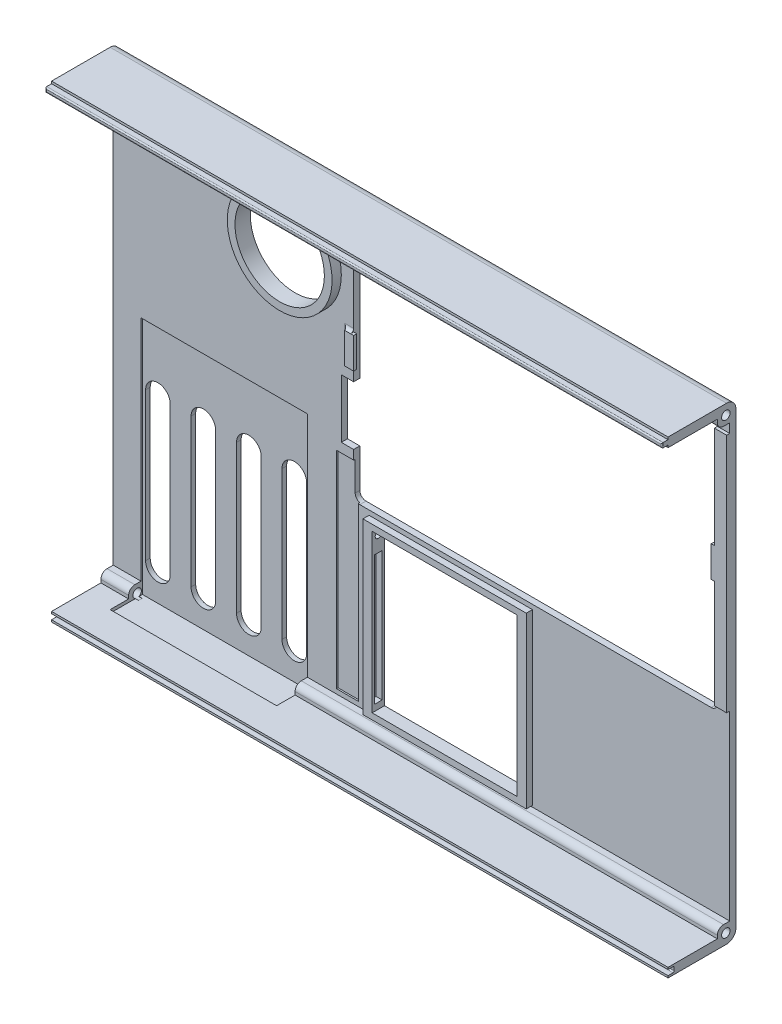
SolidWorks part; units mm, degrees
ref_plane "Front Plane" through (0, 0, 0) normal (0, 0, 1) x (1, 0, 0)
ref_plane "Top Plane" through (0, 0, 0) normal (0, 1, 0) x (1, 0, 0)
ref_plane "Right Plane" through (0, 0, 0) normal (1, 0, 0) x (0, 0, -1)
sketch "Sketch1" plane through (0, 0, 0) normal (0, 0, 1) x (1, 0, 0)
  line L1 (105, -90.3987) -> (-95, -90.3987)
  line L2 (105, -90.3987) -> (105, 61.6013)
  line L3 (105, 61.6013) -> (-95, 61.6013)
  line L4 (-95, -90.3987) -> (-95, 61.6013)
  line L5 (105, -90.3987) -> (-95, 61.6013) construction
  line L6 (105, 61.6013) -> (-95, -90.3987) construction
  point P0 (5, -14.3987)
  dimension "D1" = 200
  dimension "D2" = 152
extrude "body" add sketch "Sketch1" along normal blind 2
sketch "Sketch3" plane through (0, 0, 0) normal (0, 0, -1) x (-1, 0, 0)
  line L0 (95, -54.3987) -> (-105, -54.3987) construction
  line L1 (95, 61.6013) -> (95, -90.3987) construction
  line L2 (-105, -90.3987) -> (-105, 61.6013) construction
  line L3 (66.25, -78.3987) -> (66.25, -30.3987) construction
  line L4 (62.25, -78.3987) -> (62.25, -30.3987)
  line L5 (70.25, -78.3987) -> (70.25, -30.3987)
  line L6 (95, -30.3987) -> (-105, -30.3987) construction
  line L7 (81, -78.3987) -> (81, -30.3987) construction
  line L8 (95, -78.3987) -> (-105, -78.3987) construction
  line L9 (77, -78.3987) -> (77, -30.3987)
  line L10 (85, -78.3987) -> (85, -30.3987)
  line L11 (51.5, -78.3987) -> (51.5, -30.3987) construction
  line L12 (47.5, -78.3987) -> (47.5, -30.3987)
  line L13 (55.5, -78.3987) -> (55.5, -30.3987)
  line L14 (36.75, -78.3987) -> (36.75, -30.3987) construction
  line L15 (32.75, -78.3987) -> (32.75, -30.3987)
  line L16 (40.75, -78.3987) -> (40.75, -30.3987)
  line L17 (95, -90.3987) -> (95, 61.6013) construction
  line L18 (-105, 61.6013) -> (95, 61.6013) construction
  line L19 (95, -90.3987) -> (-105, -90.3987) construction
  line L20 (-105, -90.3987) -> (-105, 61.6013) construction
  circle A0 centre (38, 34.1013) radius 14.5
  arc A1 (62.25, -78.3987) -> (70.25, -78.3987) centre (66.25, -78.3987) ccw
  arc A2 (70.25, -30.3987) -> (62.25, -30.3987) centre (66.25, -30.3987) ccw
  arc A3 (77, -78.3987) -> (85, -78.3987) centre (81, -78.3987) ccw
  arc A4 (85, -30.3987) -> (77, -30.3987) centre (81, -30.3987) ccw
  arc A5 (47.5, -78.3987) -> (55.5, -78.3987) centre (51.5, -78.3987) ccw
  arc A6 (55.5, -30.3987) -> (47.5, -30.3987) centre (51.5, -30.3987) ccw
  arc A7 (32.75, -78.3987) -> (40.75, -78.3987) centre (36.75, -78.3987) ccw
  arc A8 (40.75, -30.3987) -> (32.75, -30.3987) centre (36.75, -30.3987) ccw
  point P10 (66.25, -54.3987)
  point P21 (81, -54.3987)
  point P27 (51.5, -54.3987)
  point P34 (36.75, -54.3987)
  dimension "D1" = 29
  dimension "D2" = 27.5
  dimension "D3" = 57
  dimension "D4" = 10
  dimension "D5" = 12
  dimension "D6" = 24
  dimension "D7" = 6.75
  dimension "D8" = 8
  dimension "D9" = 8
  dimension "D10" = 8
  dimension "D11" = 8
  dimension "D12" = 6.75
  dimension "D13" = 52.25
  dimension "D14" = 6.75
extrude "fan_exhaust_grill" cut sketch "Sketch3" against normal through all
sketch "Sketch12" plane through (0, 0, 2) normal (0, 0, 1) x (1, 0, 0)
  line L0 (-95, -90.3987) -> (-95, 61.6013) construction
  line L1 (105, -90.3987) -> (-95, -90.3987)
  line L2 (105, -90.3987) -> (105, -84.3987)
  line L3 (105, -84.3987) -> (-95, -84.3987)
  line L4 (-95, -90.3987) -> (-95, -84.3987)
  line L6 (105, 61.6013) -> (-95, 61.6013)
  line L7 (105, 61.6013) -> (105, 55.6013)
  line L8 (105, 55.6013) -> (-95, 55.6013)
  line L9 (-95, 61.6013) -> (-95, 55.6013)
  dimension "D1" = 6
  dimension "D2" = 6
extrude "side_walls" add sketch "Sketch12" along normal blind 20
sketch "Sketch14" plane through (105, 0, 0) normal (1, 0, 0) x (0, 0, -1)
  line L0 (-22, -90.3987) -> (0, -90.3987) construction
  line L1 (0, -90.3987) -> (0, 61.6013) construction
  line L2 (-22, 61.6013) -> (0, 61.6013) construction
  circle A0 centre (-3.25, -87.1487) radius 1.375
  circle A1 centre (-3.25, 58.3513) radius 1.375
  dimension "D1" = 2.75
  dimension "D2" = 2.75
  dimension "D3" = 3.25
  dimension "D4" = 3.25
  dimension "D5" = 3.25
  dimension "D6" = 3.25
  dimension "D7" = 145.5
extrude "mount_holes_l" cut sketch "Sketch14" against normal blind 10 and the other way through all
sketch "Sketch16" plane through (-95, 0, 0) normal (-1, 0, 0) x (0, 0, 1)
  line L0 (0, -90.3987) -> (0, 61.6013) construction
  line L2 (22, 61.6013) -> (0, 61.6013) construction
  line L3 (22, -90.3987) -> (0, -90.3987) construction
  circle A0 centre (3.25, -87.1487) radius 1.375
  circle A1 centre (3.25, 58.3513) radius 1.375
  dimension "D1" = 2.75
  dimension "D4" = 2.75
  dimension "D2" = 3.25
  dimension "D3" = 3.25
  dimension "D5" = 3.25
  dimension "D6" = 3.25
extrude "mount_holes_r" cut sketch "Sketch16" against normal blind 10
sketch "Sketch18" plane through (105, 0, 0) normal (1, 0, 0) x (0, 0, -1)
  line L1 (-22, -84.3987) -> (-6, -84.3987)
  line L2 (-22, -84.3987) -> (-22, -87.3987)
  line L3 (-22, -87.3987) -> (-6, -87.3987)
  line L4 (-6, -84.3987) -> (-6, -87.3987)
  line L5 (-22, 55.6013) -> (-6, 55.6013)
  line L6 (-22, 55.6013) -> (-22, 58.6013)
  line L7 (-22, 58.6013) -> (-6, 58.6013)
  line L8 (-6, 55.6013) -> (-6, 58.6013)
  dimension "D1" = 3
  dimension "D2" = 16
  dimension "D3" = 3
  dimension "D4" = 16
extrude "wall_reduce" cut sketch "Sketch18" against normal through all
sketch "Sketch19" plane through (0, 0, 22) normal (0, 0, 1) x (1, 0, 0)
  line L0 (-95, -90.3987) -> (-95, 61.6013) construction
  line L1 (-95, -89.7487) -> (105, -89.7487)
  line L2 (-95, -89.7487) -> (-95, -88.0487)
  line L3 (-95, -88.0487) -> (105, -88.0487)
  line L4 (105, -89.7487) -> (105, -88.0487)
  line L5 (105, -90.3987) -> (105, 61.6013) construction
  line L6 (-95, -90.3987) -> (105, -90.3987) construction
  line L7 (-95, -87.3987) -> (105, -87.3987) construction
  dimension "D1" = 0.65
  dimension "D2" = 1.7
  dimension "D3" = 0.65
extrude "groove" cut sketch "Sketch19" against normal blind 2
sketch "Sketch20" plane through (0, 0, 22) normal (0, 0, 1) x (1, 0, 0)
  line L0 (-95, -90.3987) -> (-95, 61.6013) construction
  line L1 (-95, 59.3513) -> (105, 59.3513)
  line L2 (-95, 59.3513) -> (-95, 60.8513)
  line L3 (-95, 60.8513) -> (105, 60.8513)
  line L4 (105, 59.3513) -> (105, 60.8513)
  line L5 (105, -90.3987) -> (105, 61.6013) construction
  line L6 (105, 61.6013) -> (-95, 61.6013) construction
  dimension "D1" = 0.75
  dimension "D2" = 1.5
extrude "notch" add sketch "Sketch20" along normal blind 2
sketch "Sketch21" plane through (0, 0, 2) normal (0, 0, 1) x (1, 0, 0)
  line L0 (105, -90.3987) -> (105, 61.6013) construction
  line L1 (101, -27.3987) -> (-17, -27.3987)
  line L2 (101, -27.3987) -> (101, 55.1013)
  line L3 (101, 55.1013) -> (-17, 55.1013)
  line L4 (-17, -27.3987) -> (-17, 55.1013)
  line L5 (105, 61.6013) -> (-95, 61.6013) construction
  dimension "D1" = 118
  dimension "D2" = 82.5
  dimension "D3" = 4
  dimension "D4" = 6.5
extrude "batt_cut" cut sketch "Sketch21" against normal through all
fillet "Fillet1" radius 3 2 edges at (5, -90.3987, 0) (5, 61.6013, 0)
fillet "Fillet2" radius 2 2 edges at (5, -84.3987, 6) (5, 55.6013, 6)
fillet "Fillet3" radius 0.4 6 edges at (5, 60.8513, 24) (105, 60.1013, 24) (5, 59.3513, 24) (-95, 60.1013, 24) (5, -89.7487, 20) (5, -88.0487, 20)
fillet "Fillet4" radius 2 4 edges at (-17, -27.3987, 1) (101, -27.3987, 1) (101, 55.1013, 1) (-17, 55.1013, 1)
sketch "Sketch22" plane through (0, 0, 2) normal (0, 0, 1) x (1, 0, 0)
  circle A0 centre (-38, 34.1013) radius 14.5
  circle A1 centre (-38, 34.1013) radius 17
  dimension "D1" = 29
  dimension "D2" = 34
extrude "fan_hole_supp" add sketch "Sketch22" along normal blind 3
sketch "Sketch23" plane through (0, 0, 2) normal (0, 0, 1) x (1, 0, 0)
  line L0 (105, -90.3987) -> (105, 61.6013) construction
  line L1 (105, 52.6013) -> (101, 52.6013)
  line L2 (105, 52.6013) -> (105, -25.3987)
  line L3 (105, -25.3987) -> (101, -25.3987)
  line L4 (101, 52.6013) -> (101, -25.3987)
  arc A0 (99, -27.3987) -> (101, -25.3987) centre (99, -25.3987) ccw construction
  dimension "D1" = 78
  dimension "D2" = 4
extrude "batt_cut_supp" add sketch "Sketch23" along normal blind 1
sketch "Sketch24" plane through (0, 0, 2) normal (0, 0, 1) x (1, 0, 0)
  line L0 (-95, -90.3987) -> (-95, 61.6013) construction
  line L1 (-86, -10.3987) -> (-32, -10.3987)
  line L2 (-86, -10.3987) -> (-86, -88.3987)
  line L3 (-86, -88.3987) -> (-32, -88.3987)
  line L4 (-32, -10.3987) -> (-32, -88.3987)
  line L5 (-95, -90.3987) -> (105, -90.3987) construction
  line L7 (-22.5, -15.8987) -> (-15.5, -15.8987)
  line L8 (-22.5, -15.8987) -> (-22.5, -82.8987)
  line L9 (-22.5, -82.8987) -> (-15.5, -82.8987)
  line L10 (-15.5, -15.8987) -> (-15.5, -82.8987)
  dimension "D1" = 9
  dimension "D2" = 2
  dimension "D3" = 54
  dimension "D4" = 78
  dimension "D5" = 9.5
  dimension "D6" = 7
  dimension "D7" = 67
  dimension "D8" = 5.5
  dimension "D9" = 5.5
extrude "Cut-Extrude1" cut sketch "Sketch24" against normal blind 10.5 from offset 10
sketch "Sketch25" plane through (0, 0, 2) normal (0, 0, 1) x (1, 0, 0)
  line L7 (-17, 53.1013) -> (-17, -15.8987) construction
  line L8 (-17, 6.1013) -> (-21, 6.1013)
  line L9 (-17, 6.1013) -> (-17, -12.8987)
  line L10 (-17, -12.8987) -> (-21, -12.8987)
  line L11 (-21, 6.1013) -> (-21, -12.8987)
  line L12 (-15, -27.3987) -> (99, -27.3987) construction
  dimension "D1" = 14.5
  dimension "D2" = 19
  dimension "D3" = 4
extrude "Cut-Extrude2" cut sketch "Sketch25" against normal through all
sketch "Sketch26" plane through (0, 0, 2) normal (0, 0, 1) x (1, 0, 0)
  line L0 (-17, 53.1013) -> (-17, 6.1013) construction
  line L1 (-17, 20.1013) -> (-19, 20.1013)
  line L2 (-17, 20.1013) -> (-17, 10.1013)
  line L3 (-17, 10.1013) -> (-19, 10.1013)
  line L4 (-19, 20.1013) -> (-19, 10.1013)
  line L10 (99, 55.1013) -> (-15, 55.1013) construction
  dimension "D4" = 2
  dimension "D5" = 10
  dimension "D6" = 35
extrude "Boss-Extrude1" add sketch "Sketch26" along normal blind 1
sketch "Sketch27" plane through (-17, 0, 0) normal (1, 0, 0) x (0, 0, -1)
  line L0 (-3, 10.1013) -> (-3, 20.1013) construction
  line L1 (-3, 20.1013) -> (-2, 20.1013)
  line L2 (-3, 20.1013) -> (-3, 10.1013)
  line L3 (-3, 10.1013) -> (-2, 10.1013)
  line L4 (-2, 20.1013) -> (-2, 10.1013)
  line L5 (-3, 20.1013) -> (-2, 20.1013) construction
extrude "Boss-Extrude2" add sketch "Sketch27" along normal blind 1
sketch "Sketch28" plane through (101, 0, 0) normal (-1, 0, 0) x (0, 0, 1)
  line L0 (0, -25.3987) -> (0, 53.1013) construction
  line L1 (2, 9.6013) -> (3, 9.6013)
  line L2 (2, 9.6013) -> (2, 19.6013)
  line L3 (2, 19.6013) -> (3, 19.6013)
  line L4 (3, 9.6013) -> (3, 19.6013)
  line L5 (3, 52.6013) -> (2, 52.6013) construction
  dimension "D1" = 1
  dimension "D2" = 2
  dimension "D3" = 10
  dimension "D4" = 33
extrude "Boss-Extrude3" add sketch "Sketch28" along normal blind 1
fillet "Fillet5" radius 1 3 edges at (-18, 20.1013, 2) (-18, 10.1013, 2) (-19, 15.1013, 2)
sketch "Sketch29" plane through (0, 0, 2) normal (0, 0, 1) x (1, 0, 0)
  line L1 (-9, -30.8987) -> (38, -30.8987)
  line L2 (-9, -30.8987) -> (-9, -81.8987)
  line L3 (-9, -81.8987) -> (38, -81.8987)
  line L4 (38, -30.8987) -> (38, -81.8987)
  line L5 (105, -90.3987) -> (105, 61.6013) construction
  line L7 (-95, -90.3987) -> (105, -90.3987) construction
  dimension "D1" = 67
  dimension "D2" = 47
  dimension "D3" = 51
  dimension "D4" = 8.5
extrude "stand_cut" cut sketch "Sketch29" against normal through all
sketch "Sketch30" plane through (0, 0, 2) normal (0, 0, 1) x (1, 0, 0)
  line L0 (-9, -81.8987) -> (38, -30.8987) construction
  line L1 (38, -30.8987) -> (-9, -30.8987) construction
  line L2 (38, -81.8987) -> (38, -30.8987) construction
  line L3 (-9, -30.8987) -> (38, -81.8987) construction
  line L5 (41, -83.8987) -> (-12, -83.8987)
  line L6 (41, -83.8987) -> (41, -28.8987)
  line L7 (41, -28.8987) -> (-12, -28.8987)
  line L8 (-12, -83.8987) -> (-12, -28.8987)
  line L9 (41, -83.8987) -> (-12, -28.8987) construction
  line L10 (41, -28.8987) -> (-12, -83.8987) construction
  line L11 (38, -81.8987) -> (-9, -81.8987)
  line L12 (38, -81.8987) -> (38, -30.8987)
  line L13 (38, -30.8987) -> (-9, -30.8987)
  line L14 (-9, -81.8987) -> (-9, -30.8987)
  line L15 (38, -81.8987) -> (-9, -30.8987) construction
  line L16 (38, -30.8987) -> (-9, -81.8987) construction
  point P11 (14.5, -56.3987)
  point P16 (14.5, -56.3987)
  dimension "D1" = 3
  dimension "D2" = 2
extrude "stand_extra_support" add sketch "Sketch30" along normal blind 2
sketch "Sketch31" plane through (-9, 0, 0) normal (1, 0, 0) x (0, 0, -1)
  line L0 (-2, -23.813) -> (-2, -81.8987) construction
  line L1 (0, -81.8987) -> (-4, -81.8987) construction
  line L2 (0, -30.8987) -> (0, -81.8987) construction
  line L3 (-0.75, -79.8987) -> (-3.25, -79.8987)
  line L4 (-0.75, -79.8987) -> (-0.75, -37.8987)
  line L5 (-0.75, -37.8987) -> (-3.25, -37.8987)
  line L6 (-3.25, -79.8987) -> (-3.25, -37.8987)
  line L7 (-0.75, -79.8987) -> (-3.25, -37.8987) construction
  line L8 (-0.75, -37.8987) -> (-3.25, -79.8987) construction
  line L9 (0, -30.8987) -> (-4, -30.8987) construction
  circle A0 centre (-2, -32.8987) radius 1
  point P4 (-2, -58.8987)
  dimension "D6" = 2
  dimension "D1" = 2
  dimension "D2" = 42
  dimension "D3" = 2.5
  dimension "D4" = 0.75
  dimension "D5" = 2
extrude "stand_right_groove" cut sketch "Sketch31" against normal blind 2
sketch "Sketch32" plane through (38, 0, 0) normal (-1, 0, 0) x (0, 0, 1)
  line L0 (2, -81.8987) -> (2, -30.8421) construction
  line L1 (0, -81.8987) -> (4, -81.8987) construction
  line L2 (0, -30.8987) -> (4, -30.8987) construction
  line L3 (3.25, -37.8987) -> (0.75, -37.8987)
  line L4 (3.25, -37.8987) -> (3.25, -79.8987)
  line L5 (3.25, -79.8987) -> (0.75, -79.8987)
  line L6 (0.75, -37.8987) -> (0.75, -79.8987)
  line L7 (3.25, -37.8987) -> (0.75, -79.8987) construction
  line L8 (3.25, -79.8987) -> (0.75, -37.8987) construction
  circle A0 centre (2, -32.8987) radius 1
  point P4 (2, -58.8987)
  dimension "D5" = 2
  dimension "D1" = 2.5
  dimension "D2" = 42
  dimension "D3" = 2
  dimension "D4" = 2
extrude "stand_left_groove" cut sketch "Sketch32" against normal blind 2
